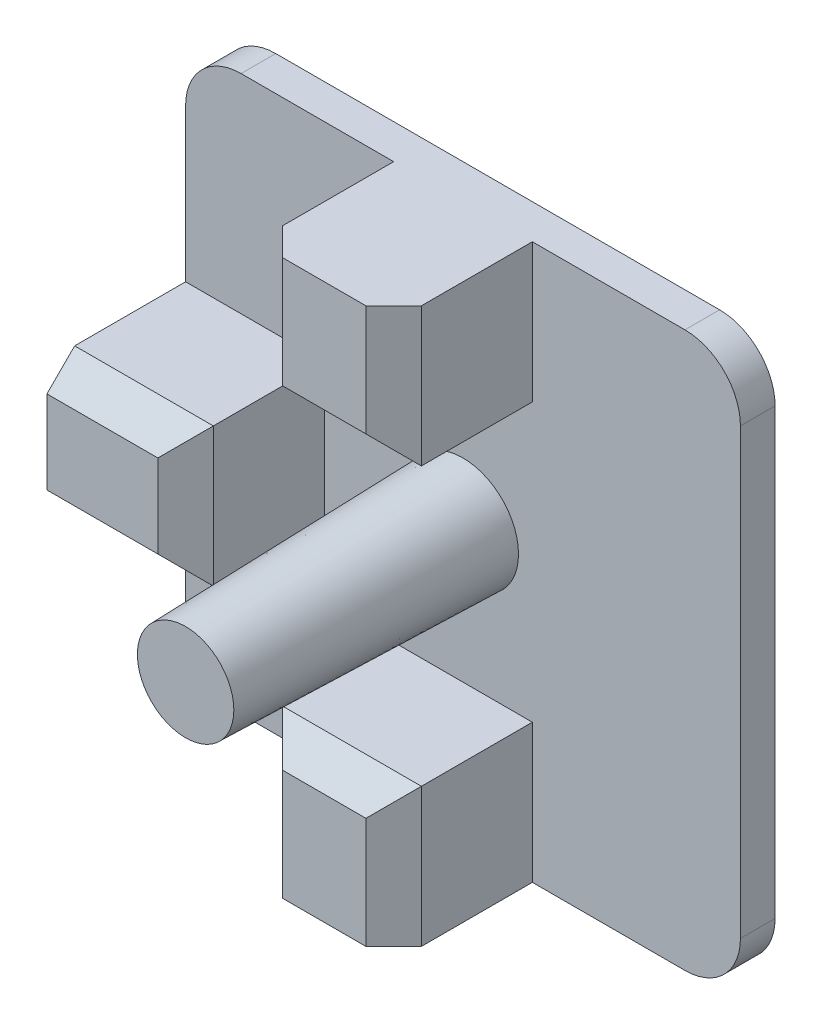
SolidWorks part; units mm, degrees
ref_plane "Front Plane" through (0, 0, 0) normal (0, 0, 1) x (1, 0, 0)
ref_plane "Top Plane" through (0, 0, 0) normal (0, 1, 0) x (1, 0, 0)
ref_plane "Right Plane" through (0, 0, 0) normal (1, 0, 0) x (0, 0, -1)
sketch "Sketch1" plane through (0, 0, 0) normal (0, 0, 1) x (1, 0, 0)
  line L1 (-10.16, 12.7) -> (10.16, 12.7)
  line L2 (-12.7, 10.16) -> (-12.7, -10.16)
  line L3 (-10.16, -12.7) -> (10.16, -12.7)
  line L4 (12.7, 10.16) -> (12.7, -10.16)
  line L5 (-12.7, 12.7) -> (12.7, -12.7) construction
  line L6 (-12.7, -12.7) -> (12.7, 12.7) construction
  arc A0 (10.16, -12.7) -> (12.7, -10.16) centre (10.16, -10.16) ccw
  arc A1 (-12.7, -10.16) -> (-10.16, -12.7) centre (-10.16, -10.16) ccw
  arc A2 (-10.16, 12.7) -> (-12.7, 10.16) centre (-10.16, 10.16) ccw
  arc A3 (10.16, 12.7) -> (12.7, 10.16) centre (10.16, 10.16) cw
  point P0 (0, 0)
  dimension "D3" = 2.54
  dimension "D1" = 25.4
  dimension "D2" = 25.4
extrude "Boss-Extrude1" add sketch "Sketch1" along normal blind 1.5875
sketch "Sketch2" plane through (0, 0, 1.5875) normal (0, 0, 1) x (1, 0, 0)
  line L0 (0, 0) -> (-12.7, 0) construction
  line L1 (-12.7, 10.16) -> (-12.7, -10.16) construction
  line L2 (0, 0) -> (0, -12.7) construction
  line L3 (-10.16, -12.7) -> (10.16, -12.7) construction
  line L4 (-12.7, -3.175) -> (-6.35, -3.175)
  line L5 (-6.35, -3.175) -> (-6.35, 3.175)
  line L6 (-6.35, 3.175) -> (-12.7, 3.175)
  line L7 (3.175, 6.35) -> (3.175, 12.7)
  line L8 (-3.175, 6.35) -> (3.175, 6.35)
  line L9 (-3.175, 12.7) -> (-3.175, 6.35)
  line L10 (6.35, -3.175) -> (12.7, -3.175)
  line L11 (6.35, 3.175) -> (6.35, -3.175)
  line L12 (12.7, 3.175) -> (6.35, 3.175)
  line L13 (-3.175, -6.35) -> (-3.175, -12.7)
  line L14 (3.175, -6.35) -> (-3.175, -6.35)
  line L15 (3.175, -12.7) -> (3.175, -6.35)
  circle A0 centre (0, 0) radius 2.54
  line M9 (10.16, 12.7) -> (-10.16, 12.7)
  line M11 (-12.7, 10.16) -> (-12.7, -10.16)
  line M13 (-10.16, -12.7) -> (10.16, -12.7)
  dimension "D1" = 5.08
  dimension "D2" = 6.35
  dimension "D3" = 3.175
  dimension "D4" = 6.35
  dimension "D5" = 4
extrude "Boss-Extrude3" add sketch "Sketch2" along normal blind 6.35 contours L15 L14 L13 M13 | L5 L6 L4 M11 | L9 L8 L7 M9 region at (-9.525, 0, 1.5875) region at (0, 9.525, 1.5875) region at (0, -9.525, 1.5875)
extrude "Boss-Extrude4" add sketch "Sketch2<4>" along normal blind 12.7 draft 1.5 contours A0 region at (0, 0, 1.5875)
sketch "Sketch2<4>" plane through (0, 0, 1.5875) normal (0, 0, 1) x (1, 0, 0) same geometry as "Sketch2"
chamfer "Chamfer1" distance 1.27 angle 45 9 edges at (3.175, 9.525, 7.9375) (-3.175, 9.525, 7.9375) (0, 6.35, 7.9375) (-9.525, -3.175, 7.9375) (-9.525, 3.175, 7.9375) (-6.35, 0, 7.9375) (-3.175, -9.525, 7.9375) (3.175, -9.525, 7.9375) (0, -6.35, 7.9375)
